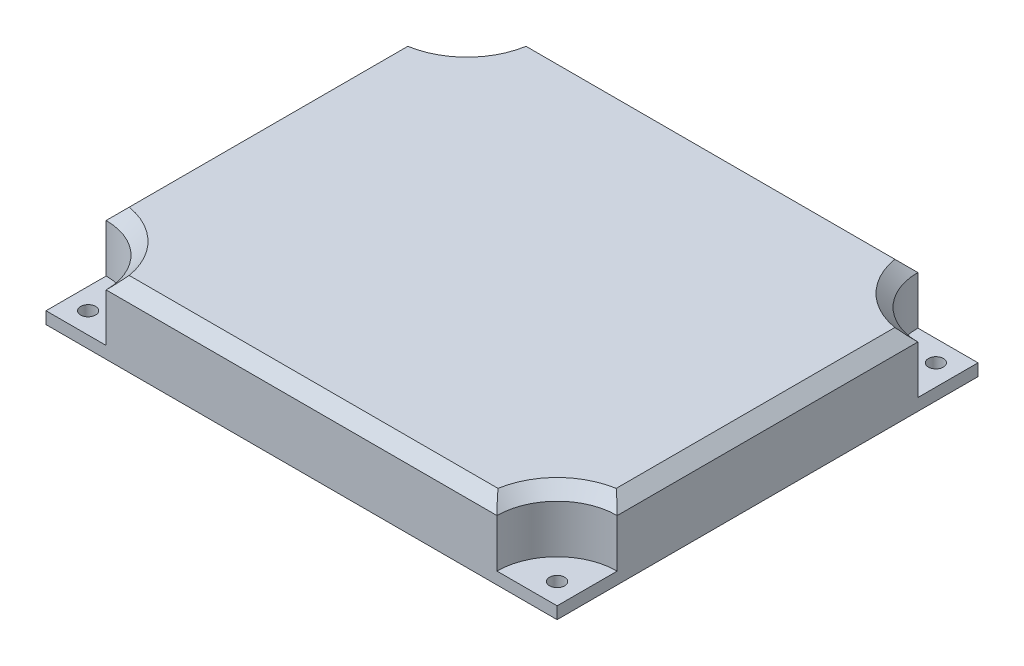
SolidWorks part; units mm, degrees
material "6061-T6 (SS)"
ref_plane "Front Plane" through (0, 0, 0) normal (0, 0, 1) x (1, 0, 0)
ref_plane "Top Plane" through (0, 0, 0) normal (0, 1, 0) x (1, 0, 0)
ref_plane "Right Plane" through (0, 0, 0) normal (1, 0, 0) x (0, 0, -1)
sketch "Sketch2" plane through (0, 0, 0) normal (0, 1, 0) x (1, 0, 0)
  line L1 (-42.5, -35) -> (42.5, -35)
  line L2 (-42.5, -35) -> (-42.5, 35)
  line L3 (-42.5, 35) -> (42.5, 35)
  line L4 (42.5, -35) -> (42.5, 35)
  line L5 (-42.5, -35) -> (42.5, 35) construction
  line L6 (-42.5, 35) -> (42.5, -35) construction
  point P0 (0, 0)
  dimension "D1" = 85
  dimension "D2" = 70
extrude "Boss-Extrude1" add sketch "Sketch2" along normal blind 12
sketch "Sketch3" plane through (0, 0, 0) normal (0, -1, 0) x (1, 0, 0)
  line L1 (-39, -39) -> (39, -39)
  line L2 (-39, -39) -> (-39, 39)
  line L3 (-39, 39) -> (39, 39)
  line L4 (39, -39) -> (39, 39)
  line L5 (-39, -39) -> (39, 39) construction
  line L6 (-39, 39) -> (39, -39) construction
  point P0 (0, 0)
  dimension "D1" = 78
  dimension "D2" = 78
extrude "Cut-Extrude1" [suppressed] cut sketch "Sketch3" against normal blind 10
ref_plane "Plane1" through (0, 0, 6) normal (0, 0, -1) x (-1, 0, 0)
ref_plane "Plane2" through (0, 0, 0) normal (1, 0, 0) x (0, 0, -1)
fillet "Fillet1" [suppressed] radius 2
sketch "Sketch4" plane through (0, 12, 0) normal (0, 1, 0) x (1, 0, 0)
  line L5 (0, 0) -> (43.0078, 0) construction
  circle A1 centre (42.5, -35) radius 10
  circle A2 centre (-42.5, -35) radius 10
  circle A3 centre (-42.5, 35) radius 10
  circle A4 centre (42.5, 35) radius 10
  dimension "D1" = 20
extrude "Cut-Extrude3" cut sketch "Sketch4" against normal blind 10 contours A1 | A2 | A3 | A4
sketch "Sketch5" plane through (0, 2, 0) normal (0, 1, 0) x (1, 0, 0)
  line L4 (-42.5, -25) -> (-42.5, -35) construction
  line L5 (-42.5, -35) -> (-32.5, -35) construction
  line L6 (42.5, -35) -> (42.5, -25) construction
  line L7 (32.5, -35) -> (42.5, -35) construction
  line L8 (32.5, 35) -> (42.5, 35) construction
  line L9 (42.5, 35) -> (42.5, 25) construction
  line L10 (-42.5, 35) -> (-32.5, 35) construction
  line L11 (-42.5, 25) -> (-42.5, 35) construction
  point P20 (-39, 31.5)
  point P21 (-39, -31.5)
  point P22 (39, -31.5)
  point P23 (39, 31.5)
  dimension "D1" = 3.5
  dimension "D2" = 3.5
  dimension "D3" = 3.5
  dimension "D4" = 3.5
  dimension "D5" = 3.5
  dimension "D6" = 3.5
  dimension "D7" = 3.5
  dimension "D8" = 3.5
sketch "Sketch8" plane through (0, 0, 0) normal (0, -1, 0) x (1, 0, 0)
  line L2 (-42.5, 35) -> (42.5, 35) construction
  line L3 (35.95, -26.45) -> (35.95, 26.45)
  line L4 (34.95, 27.45) -> (-34.95, 27.45)
  line L5 (-35.95, 26.45) -> (-35.95, -26.45)
  line L6 (-34.95, -27.45) -> (34.95, -27.45)
  line L7 (-42.5, -35) -> (-42.5, 35) construction
  arc A0 (35.95, 26.45) -> (34.95, 27.45) centre (34.95, 26.45) ccw
  arc A1 (-34.95, 27.45) -> (-35.95, 26.45) centre (-34.95, 26.45) ccw
  arc A2 (-35.95, -26.45) -> (-34.95, -27.45) centre (-34.95, -26.45) ccw
  arc A3 (35.95, -26.45) -> (34.95, -27.45) centre (34.95, -26.45) cw
  point P14 (0, 35)
  point P15 (0, 27.45)
  point P16 (0, -27.45)
  point P19 (-42.5, 0)
  point P20 (-35.95, 0)
  point P21 (35.95, 0)
  dimension "D1" = 1
  dimension "D2" = 54.9
  dimension "D3" = 71.9
fillet "Fillet2" radius 2 8 edges at (42.5, 12, 0) (35.4289, 12, 27.9289) (0, 12, 35) (-35.4289, 12, 27.9289) (-42.5, 12, 0) (-35.4289, 12, -27.9289) (0, 12, -35) (35.4289, 12, -27.9289) profile chamfer
hole_wizard "M3x0.5 Tapped Hole1" positions "Sketch9" profile "Sketch10" tap size "M3x0.5" standard "ANSI Metric"
sketch "Sketch9" plane through (0, 2, 0) normal (0, 1, 0) x (1, 0, 0)
  point P0 (-39, 31.5)
  point P3 (-39, -31.5)
  point P6 (39, -31.5)
  point P9 (39, 31.5)
sketch "Sketch10" plane through (-39, 2, -31.5) normal (1, 0, 0) x (0, 0, 1)
  line L0 (0, 0) -> (0, 10.7511)
  line L1 (0, 10.7511) -> (1.25, 10)
  line L2 (1.25, 10) -> (1.25, 0)
  line L5 (1.25, 0) -> (0, 0)
  line L10 (0, 10.7511) -> (-1.25, 10) construction
  line L11 (0, -6.35) -> (0, 107.95) construction
  dimension "Tap Drill Dia." = 2.5
  dimension "Tap Drill Depth" = 10
  dimension "Drill Angle" = 118
extrude "Cut-Extrude4" cut sketch "Sketch8" against normal blind 8
